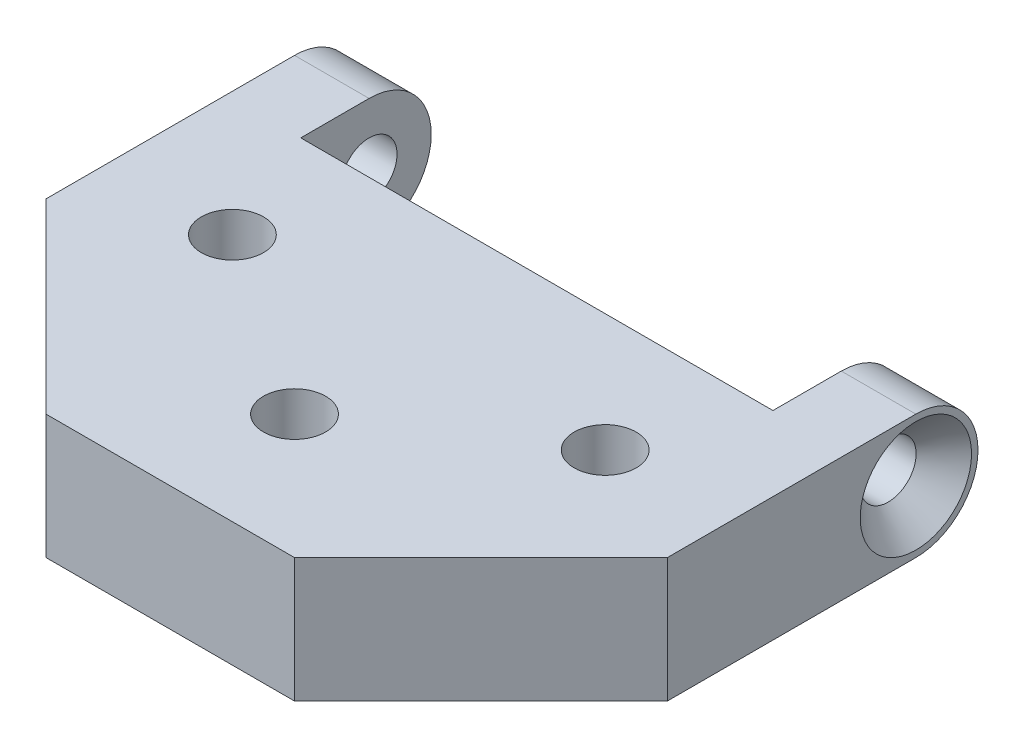
SolidWorks part; units mm, degrees
ref_plane "Front Plane" through (0, 0, 0) normal (0, 0, 1) x (1, 0, 0)
ref_plane "Top Plane" through (0, 0, 0) normal (0, 1, 0) x (1, 0, 0)
ref_plane "Right Plane" through (0, 0, 0) normal (1, 0, 0) x (0, 0, -1)
sketch "Sketch1" plane through (0, 0, 0) normal (0, 1, 0) x (1, 0, 0)
  line L1 (-25, -20) -> (25, -20)
  line L2 (-25, -20) -> (-25, 20)
  line L3 (-25, 20) -> (25, 20)
  line L4 (25, -20) -> (25, 20)
  line L5 (-25, -20) -> (25, 20) construction
  line L6 (-25, 20) -> (25, -20) construction
  line L7 (-19, 9.5) -> (19, 9.5)
  line L8 (-19, 9.5) -> (-19, 20)
  line L9 (-19, 20) -> (19, 20)
  line L10 (19, 9.5) -> (19, 20)
  line L11 (-19, 9.5) -> (19, 20) construction
  line L12 (-19, 20) -> (19, 9.5) construction
  point P0 (0, 0)
  point P6 (0, 14.75)
  dimension "D1" = 40
  dimension "D2" = 50
  dimension "D3" = 6
  dimension "D4" = 10.5
extrude "Boss-Extrude1" add sketch "Sketch1" along normal blind 10 contours L10 L7 L8 L3 L2 L1 L4 region at (0, 0, 3.676)
fillet "Fillet1" radius 5 4 edges at (22, 10, -20) (22, 0, -20) (-22, 0, -20) (-22, 10, -20)
hole_wizard "CSK for M4 SFHCS1" positions "Sketch2" profile "Sketch3" countersink size "M4" standard "ANSI Metric"
sketch "Sketch2" plane through (25, 0, 0) normal (1, 0, 0) x (0, 0, -1)
  point P0 (15, 5)
sketch "Sketch3" plane through (25, 5, -15) normal (0, 1, 0) x (0, 0, -1)
  line L0 (0, 0) -> (0, 11.3519)
  line L1 (0, 11.3519) -> (2.25, 10)
  line L2 (2.25, 10) -> (2.25, 2.23)
  line L3 (2.25, 2.23) -> (4.48, 0)
  line L5 (4.48, 0) -> (0, 0)
  line L6 (-2.25, 2.23) -> (-4.48, 0) construction
  line L10 (0, 11.3519) -> (-2.25, 10) construction
  line L11 (0, -6.35) -> (0, 107.95) construction
  dimension "Hole Dia." = 4.5
  dimension "Hole Depth" = 10
  dimension "Near C'Sink Dia." = 8.96
  dimension "Near C'Sink Angle" = 90
  dimension "Drill Angle" = 118
mirror "Mirror1" about plane through (0, 0, 0) normal (1, 0, 0) of "CSK for M4 SFHCS1"
hole_wizard "CBORE for M5 Hex Head Bolt1" positions "Sketch4" profile "Sketch6" counterbore size "M5" standard "ANSI Metric"
sketch "Sketch4" plane through (0, 10, 0) normal (0, 1, 0) x (1, 0, 0)
  line L0 (-15, 0) -> (15, 0)
  line L1 (-25, -20) -> (25, -20) construction
  point P1 (-15, 0)
  point P2 (15, 0)
  point P5 (0, -10)
  point P13 (0, 0)
  dimension "D1" = 30
  dimension "D2" = 10
  dimension "D3" = 10
sketch "Sketch6" plane through (-15, 10, 0) normal (1, 0, 0) x (0, 0, 1)
  line L0 (0, 0) -> (0, 11.3519)
  line L1 (0, 11.3519) -> (2.25, 10)
  line L2 (2.25, 10) -> (2.25, 4.2)
  line L3 (2.25, 4.2) -> (2.5, 4.2)
  line L4 (2.5, 4.2) -> (2.5, 0)
  line L5 (2.5, 0) -> (0, 0)
  line L10 (0, 11.3519) -> (-2.25, 10) construction
  line L11 (0, -6.35) -> (0, 107.95) construction
  dimension "Hole Dia." = 4.5
  dimension "Hole Depth" = 10
  dimension "C'Bore Dia." = 5
  dimension "C'Bore Depth" = 4.2
  dimension "Drill Angle" = 118
chamfer "Chamfer1" distance 15 angle 45 2 edges at (-25, 5, 20) (25, 5, 20)
